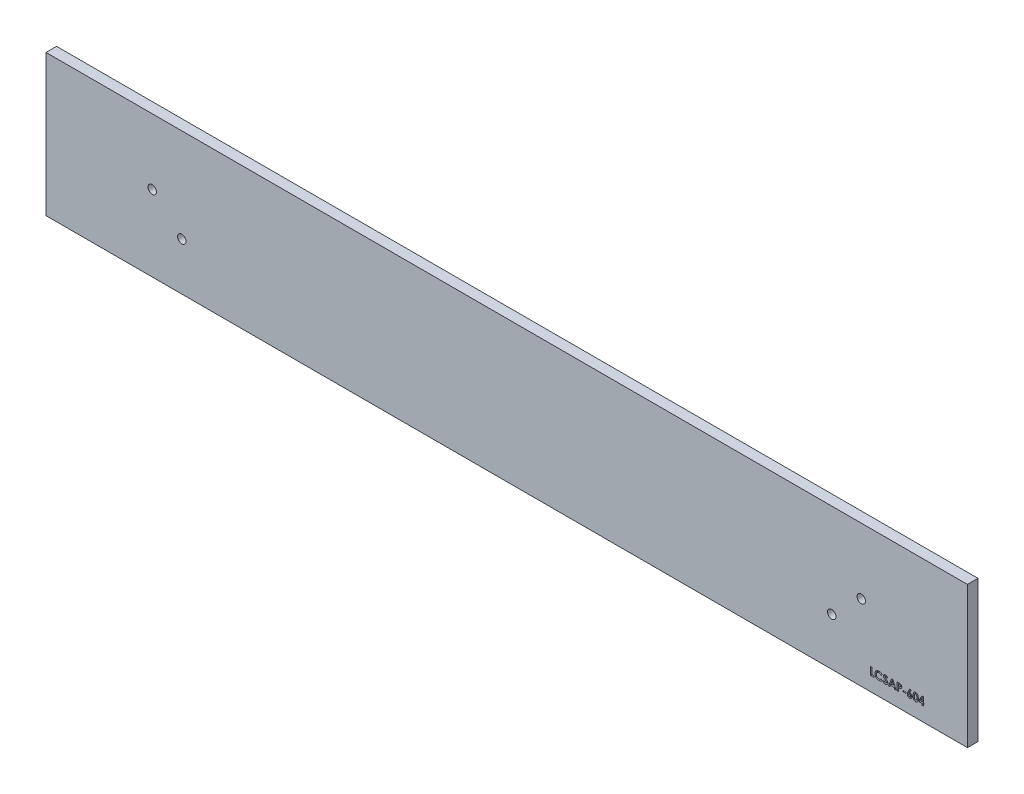
SolidWorks part; units mm, degrees
ref_plane "Front (1)" through (0, 0, 0) normal (0, 0, 1) x (1, 0, 0)
ref_plane "Top (2)" through (0, 0, 0) normal (0, 1, 0) x (1, 0, 0)
ref_plane "Right (3)" through (0, 0, 0) normal (1, 0, 0) x (0, 0, -1)
ref_axis "X-Axis" through (-80.9, 0, 0) along (1, 0, 0)
ref_axis "Y-Axis" through (0, -50, 0) along (0, 1, 0)
ref_axis "Z-Axis" through (0, 0, 50) along (0, 0, -1)
sketch "Sketch1" plane through (0, 0, 0) normal (0, 0, 1) x (1, 0, 0)
  line L1 (0, 0) -> (415.925, 0)
  line L2 (0, 0) -> (0, 63.8175)
  line L3 (0, 63.8175) -> (415.925, 63.8175)
  line L4 (415.925, 0) -> (415.925, 63.8175)
  dimension "D1" = 415.925
  dimension "D2" = 63.8175
extrude "Boss-Extrude1" add sketch "Sketch1" along normal blind 4.7625
sketch "Sketch2" plane through (0, 0, 0) normal (0, 0, -1) x (-1, 0, 0)
  line L0 (-367.9825, 34.2265) -> (-207.9625, 0) construction
  line L1 (0, 0) -> (-415.925, 0) construction
  line L2 (-207.9625, 0) -> (-47.9425, 34.2265) construction
  line L3 (-354.6475, 21.5265) -> (-207.9625, 63.8175) construction
  line L4 (-415.925, 63.8175) -> (0, 63.8175) construction
  line L5 (-207.9625, 63.8175) -> (-61.2775, 21.5265) construction
  circle A0 centre (-367.9825, 34.2265) radius 1.905
  circle A1 centre (-354.6475, 21.5265) radius 1.905
  circle A2 centre (-47.9425, 34.2265) radius 1.905
  circle A3 centre (-61.2775, 21.5265) radius 1.905
  dimension "D9" = 3.81
  dimension "D1" = 293.37
  dimension "D2" = 21.5265
  dimension "D3" = 320.04
  dimension "D4" = 12.7
  dimension "D5" = 21.5265
  dimension "D8" = 12.7
extrude "Cut-Extrude1" cut sketch "Sketch2" against normal through all
sketch "Sketch3" plane through (0, 0, 4.7625) normal (0, 0, 1) x (1, 0, 0)
  line L0 (415.925, 6.35) -> (352.425, 6.35) construction
  line L1 (415.925, 0) -> (415.925, 63.8175) construction
  line L2 (0, 0) -> (415.925, 0) construction
  text T0 "<b>LCSAP-604</b>"
  dimension "D1" = 6.35
  dimension "D2" = 63.5
extrude "Cut-Extrude2" cut sketch "Sketch3" against normal blind 1.016
